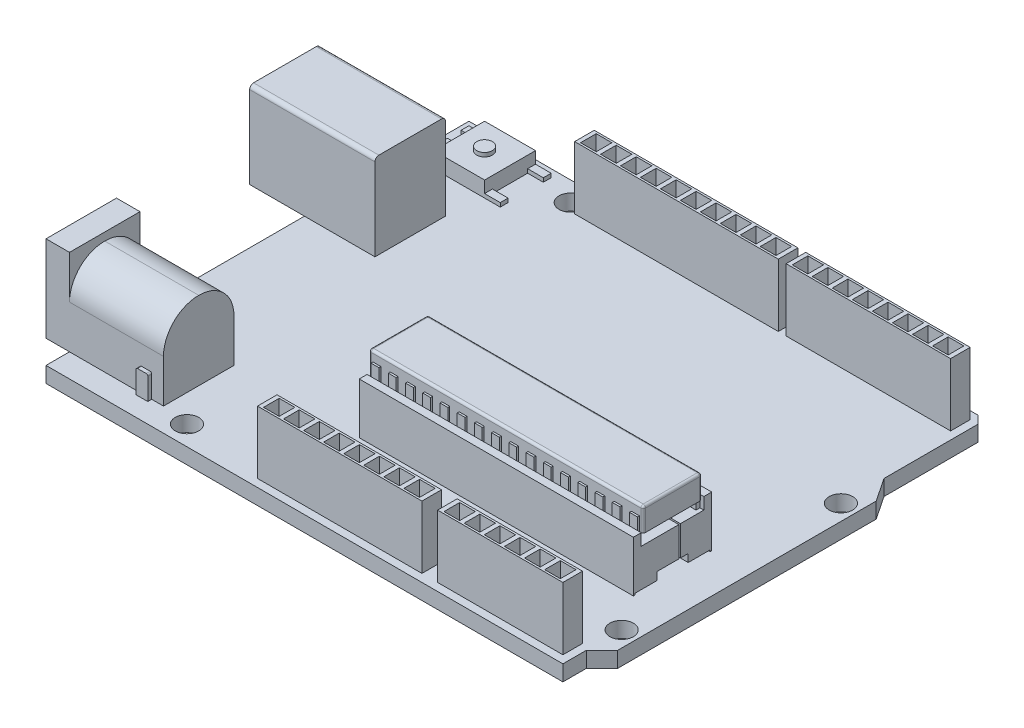
SolidWorks part; units mm, degrees
ref_plane "Ön Düzlem" through (0, 0, 0) normal (0, 0, 1) x (1, 0, 0)
ref_plane "Üst Düzlem" through (0, 0, 0) normal (0, 1, 0) x (1, 0, 0)
ref_plane "Sağ Düzlem" through (0, 0, 0) normal (1, 0, 0) x (0, 0, -1)
sketch "Çizim2" plane through (0, 0, 0) normal (0, 1, 0) x (1, 0, 0)
  line L0 (32, -27) -> (32, -19.8418) construction
  line L1 (-34, 27) -> (31, 27)
  line L2 (-34, 27) -> (-34, -27)
  line L3 (-34, -27) -> (32, -27)
  line L4 (34, 11) -> (34, -22)
  line L5 (-34, 27) -> (32, -25.4118) construction
  line L6 (-34, -27) -> (32, 25.4118) construction
  line L7 (32, -27) -> (32, -24)
  line L8 (32, -24) -> (34, -22)
  line L9 (32, 27) -> (32, 12.4131) construction
  line L10 (34, 11) -> (32, 14)
  line L11 (32, 14) -> (32, 26)
  line L12 (31, 27) -> (32, 26)
  line L13 (32, 14) -> (32, -24) construction
  line L14 (34, -22) -> (-34, -22) construction
  line L15 (-17, 27) -> (-17, 17.3329) construction
  line L16 (-34, 26) -> (4.5999, 26) construction
  line L17 (-18.5, 24.5) -> (-18.5, -27) construction
  circle A0 centre (32, -19.5) radius 1.5
  circle A1 centre (32, 8.5) radius 1.5
  circle A2 centre (-18.5, 24.5) radius 1.5
  circle A3 centre (-18.5, -24.5) radius 1.5
  point P0 (0, 0)
  point P1 (34, 11)
  point P6 (32, -27)
  point P7 (34, -22)
  point P10 (32, -24)
  point P14 (32, 27)
  point P15 (32, 14)
  point P27 (-17, 27)
  dimension "D1" = 3
  dimension "D7" = 3
  dimension "D9" = 28
  dimension "D10" = 2.5
  dimension "D13" = 3
  dimension "D14" = 3
  dimension "D2" = 33
  dimension "D3" = 66
  dimension "D4" = 66
  dimension "D5" = 3
  dimension "D6" = 13
  dimension "D11" = 49
  dimension "D12" = 1
  dimension "D15" = 2.5
extrude "Yükseklik-Ekstrüzyon1" add sketch "Çizim2" along normal blind 2
sketch "Çizim3" plane through (0, 2, 0) normal (0, 1, 0) x (1, 0, 0)
  line L0 (-34, 27) -> (-34, -27) construction
  line L1 (-31, 26) -> (-24.5, 26)
  line L2 (-31, 26) -> (-31, 19.5)
  line L3 (-31, 19.5) -> (-24.5, 19.5)
  line L4 (-24.5, 26) -> (-24.5, 19.5)
  line L5 (-31, 26) -> (-24.5, 19.5) construction
  line L6 (-31, 19.5) -> (-24.5, 26) construction
  line L7 (31, 27) -> (-34, 27) construction
  point P0 (-27.75, 22.75)
  dimension "D1" = 6.5
  dimension "D2" = 6.5
  dimension "D3" = 3
  dimension "D4" = 1
extrude "Yükseklik-Ekstrüzyon2" add sketch "Çizim3" along normal blind 2
sketch "Çizim4" plane through (0, 4, 0) normal (0, 1, 0) x (1, 0, 0)
  line L0 (-31, 26) -> (-24.5, 19.5) construction
  circle A0 centre (-27.75, 22.75) radius 1
  dimension "D1" = 2
extrude "Yükseklik-Ekstrüzyon3" add sketch "Çizim4" along normal blind 0.5
sketch "Çizim5" plane through (0, 2, 0) normal (0, 1, 0) x (1, 0, 0)
  line L1 (-34, 27) -> (-34, -27) construction
  line L2 (-31, 26) -> (-31, 19.5) construction
  line L3 (-31, 23.25) -> (-33, 23.25)
  line L4 (-31, 26) -> (-33, 26)
  line L5 (-31, 22.25) -> (-33, 22.25)
  line L6 (-33, 23.25) -> (-33, 22.25)
  line L7 (-31, 22.75) -> (-33, 22.25) construction
  line L8 (-31, 22.75) -> (-33, 23.25) construction
  line L9 (-31, 23.25) -> (-31, 22.25)
  line L10 (-31, 22.75) -> (-34, 22.75) construction
  line L11 (-31, 26) -> (-31, 25)
  line L12 (-31, 25) -> (-33, 25)
  line L13 (-33, 26) -> (-33, 25)
  line L14 (-31, 19.5) -> (-33, 19.5)
  line L15 (-31, 19.5) -> (-31, 20.5)
  line L16 (-31, 20.5) -> (-33, 20.5)
  line L17 (-33, 19.5) -> (-33, 20.5)
  line L18 (-24.5, 26) -> (-22.5, 26)
  line L19 (-24.5, 26) -> (-24.5, 25)
  line L20 (-24.5, 25) -> (-22.5, 25)
  line L21 (-22.5, 26) -> (-22.5, 25)
  line L22 (-24.5, 19.5) -> (-22.5, 19.5)
  line L23 (-24.5, 19.5) -> (-24.5, 20.5)
  line L24 (-24.5, 20.5) -> (-22.5, 20.5)
  line L25 (-22.5, 19.5) -> (-22.5, 20.5)
  point P5 (-31, 22.75)
  dimension "D1" = 1
  dimension "D2" = 1
  dimension "D3" = 1
  dimension "D4" = 1
  dimension "D5" = 2
extrude "Yükseklik-Ekstrüzyon4" add sketch "Çizim5" along normal blind 0.5
sketch "Çizim6" plane through (0, 2, 0) normal (0, 1, 0) x (1, 0, 0)
  line L0 (-34, 6) -> (34, 6) construction
  line L1 (-34, 27) -> (-34, -27) construction
  line L2 (34, -22) -> (34, 11) construction
  line L3 (31, 27) -> (-34, 27) construction
  line L5 (-25, 6) -> (-41, 6)
  line L6 (-25, 6) -> (-25, 15)
  line L7 (-25, 15) -> (-41, 15)
  line L8 (-41, 6) -> (-41, 15)
  point P8 (-25, 6)
  dimension "D1" = 21
  dimension "D2" = 9
  dimension "D3" = 16
  dimension "D4" = 9
extrude "Yükseklik-Ekstrüzyon5" add sketch "Çizim6" along normal blind 11
sketch "Çizim7" plane through (-41, 0, 0) normal (-1, 0, 0) x (0, 0, 1)
  line L0 (-14, 3.5) -> (-7, 3.5)
  line L1 (-15, 13) -> (-15, 2) construction
  line L2 (-6, 13) -> (-6, 2) construction
  line L3 (-15, 2) -> (-6, 2) construction
  line L4 (-14, 3.5) -> (-14, 10.5)
  line L5 (-15, 13) -> (-6, 13) construction
  line L6 (-12.5, 12) -> (-8.5, 12)
  line L7 (-7, 10.5) -> (-7, 3.5)
  line L9 (-8.5, 12) -> (-7, 10.5)
  line L10 (-14, 10.5) -> (-12.5, 12)
  point P12 (-14, 12)
  point P19 (-7, 12)
  point P20 (-14, 12)
  dimension "D1" = 1.5
  dimension "D2" = 1
  dimension "D3" = 1
  dimension "D5" = 1
extrude "Kes-Ekstrüzyon1" cut sketch "Çizim7" against normal blind 11
sketch "Çizim8" plane through (-30, 0, 0) normal (-1, 0, 0) x (0, 0, 1)
  line L0 (-14, 7) -> (-7, 7) construction
  line L1 (-14, 10.5) -> (-14, 3.5) construction
  line L2 (-7, 3.5) -> (-7, 10.5) construction
  line L4 (-13.25, 8.5) -> (-7.75, 8.5)
  line L5 (-13.25, 8.5) -> (-13.25, 5.5)
  line L6 (-13.25, 5.5) -> (-7.75, 5.5)
  line L7 (-7.75, 8.5) -> (-7.75, 5.5)
  line L8 (-13.25, 8.5) -> (-7.75, 5.5) construction
  line L9 (-13.25, 5.5) -> (-7.75, 8.5) construction
  point P6 (-10.5, 7)
  dimension "D1" = 5.5
  dimension "D2" = 3
extrude "Yükseklik-Ekstrüzyon6" add sketch "Çizim8" along normal blind 11
fillet "Radyus1" radius 0.5 1 edges at (-33, 13, -6)
fillet "Radyus2" radius 0.5 1 edges at (-33, 13, -15)
sketch "Çizim9" plane through (0, 2, 0) normal (0, 1, 0) x (1, 0, 0)
  line L0 (-34, -24) -> (8.4522, -24) construction
  line L3 (-34, 6) -> (-34, -27) construction
  line L4 (-34, -27) -> (32, -27) construction
  line L6 (-34, -24) -> (-22, -24)
  line L7 (-34, -24) -> (-34, -15)
  line L8 (-34, -15) -> (-22, -15)
  line L9 (-22, -24) -> (-22, -15)
  dimension "D1" = 3
  dimension "D2" = 12
  dimension "D3" = 9
extrude "Yükseklik-Ekstrüzyon7" add sketch "Çizim9" along normal blind 10
fillet "Radyus3" radius 4.5 1 edges at (-28, 12, 15)
fillet "Radyus4" radius 4.5 3 edges at (-28, 12, 24) (-22, 12, 21.75) (-34, 12, 21.75)
sketch "Çizim10" plane through (-34, 0, 0) normal (-1, 0, 0) x (0, 0, 1)
  line L1 (15, 2) -> (24, 2)
  line L2 (15, 2) -> (15, 13)
  line L3 (15, 13) -> (24, 13)
  line L4 (24, 2) -> (24, 13)
  dimension "D1" = 11
  dimension "D2" = 9
extrude "Yükseklik-Ekstrüzyon8" add sketch "Çizim10" along normal blind 3
sketch "Çizim11" plane through (-37, 0, 0) normal (-1, 0, 0) x (0, 0, 1)
  line L0 (15, 8) -> (24, 8) construction
  line L1 (15, 13) -> (15, 2) construction
  line L2 (24, 2) -> (24, 13) construction
  line L3 (24, 13) -> (15, 13) construction
  circle A0 centre (19.5, 8) radius 3
  dimension "D2" = 6
  dimension "D1" = 5
extrude "Kes-Ekstrüzyon2" cut sketch "Çizim11" against normal blind 8
sketch "Çizim12" plane through (-29, 0, 0) normal (-1, 0, 0) x (0, 0, 1)
  circle A0 centre (19.5, 8) radius 0.5
  dimension "D1" = 1
extrude "Yükseklik-Ekstrüzyon9" add sketch "Çizim12" along normal blind 7 contours A0
sketch "Çizim13" plane through (0, 0, 24) normal (0, 0, 1) x (1, 0, 0)
  line L0 (-34, 2) -> (-22, 2) construction
  line L1 (-25, 2) -> (-23.5, 2)
  line L2 (-25, 2) -> (-25, 5)
  line L3 (-25, 5) -> (-23.5, 5)
  line L4 (-23.5, 2) -> (-23.5, 5)
  line L5 (-22, 7.5) -> (-22, 2) construction
  dimension "D1" = 3
  dimension "D2" = 1.5
  dimension "D3" = 1.5
extrude "Yükseklik-Ekstrüzyon10" add sketch "Çizim13" along normal blind 0.5
fillet "Radyus5" radius 0.2 1 edges at (-23.5, 5, 24.25)
fillet "Radyus6" radius 0.2 1 edges at (-25, 5, 24.25)
sketch "Çizim15" plane through (0, 0, 15) normal (0, 0, -1) x (-1, 0, 0)
  line L0 (22, 2) -> (34, 2) construction
  line L1 (23.5, 2) -> (25, 2)
  line L2 (23.5, 2) -> (23.5, 5)
  line L3 (23.5, 5) -> (25, 5)
  line L4 (25, 2) -> (25, 5)
  line L5 (22, 7.5) -> (22, 2) construction
  dimension "D1" = 1.5
  dimension "D2" = 1.5
  dimension "D3" = 3
extrude "Yükseklik-Ekstrüzyon11" add sketch "Çizim15" along normal blind 0.5
fillet "Radyus7" radius 0.2 1 edges at (-23.5, 5, 14.75)
fillet "Radyus8" radius 0.2 1 edges at (-25, 5, 14.75)
fillet "Radyus9" radius 0.3 1 edges at (-36, 8, 20)
sketch "Çizim16" plane through (0, 2, 0) normal (0, 1, 0) x (1, 0, 0)
  line L0 (34, -15) -> (9.0566, -15) construction
  line L1 (34, -22) -> (34, 11) construction
  line L2 (-34, -27) -> (32, -27) construction
  line L4 (29, -15) -> (-6, -15)
  line L5 (29, -15) -> (29, -5)
  line L6 (29, -5) -> (-6, -5)
  line L7 (-6, -15) -> (-6, -5)
  dimension "D1" = 12
  dimension "D2" = 5
  dimension "D3" = 10
  dimension "D4" = 35
extrude "Yükseklik-Ekstrüzyon12" add sketch "Çizim16" along normal blind 5
sketch "Çizim17" plane through (0, 7, 0) normal (0, 1, 0) x (1, 0, 0)
  line L0 (29, -15) -> (29, -5) construction
  line L1 (-6, -5) -> (29, -5)
  line L2 (-6, -5) -> (-6, -6)
  line L3 (-6, -6) -> (29, -6)
  line L4 (29, -5) -> (29, -6)
  line L5 (-6, -5) -> (-6, -15) construction
  line L6 (29, -15) -> (-6, -15)
  line L7 (29, -15) -> (29, -14)
  line L8 (29, -14) -> (-6, -14)
  line L9 (-6, -15) -> (-6, -14)
  dimension "D1" = 1
  dimension "D2" = 1
extrude "Yükseklik-Ekstrüzyon13" add sketch "Çizim17" along normal blind 1.5
sketch "Çizim18" plane through (0, 7, 0) normal (0, 1, 0) x (1, 0, 0)
  line L0 (-6, -10) -> (9.4618, -10) construction
  line L1 (-6, -5) -> (-6, -15) construction
  line L2 (-6, -6) -> (29, -6) construction
  line L3 (-5.5, -6) -> (-4.5, -6)
  line L4 (-5.5, -6) -> (-5.5, -6.5)
  line L5 (-5.5, -6.5) -> (-4.5, -6.5)
  line L6 (-4.5, -6) -> (-4.5, -6.5)
  line L7 (-6, -6) -> (-6, -14) construction
  line L8 (-3.3, -6) -> (-3.3, -6.5)
  line L9 (-3.3, -6.5) -> (-2.3, -6.5)
  line L10 (-3.3, -6) -> (-2.3, -6)
  line L11 (-2.3, -6) -> (-2.3, -6.5)
  line L12 (-1.1, -6) -> (-1.1, -6.5)
  line L13 (-1.1, -6.5) -> (-0.1, -6.5)
  line L14 (-1.1, -6) -> (-0.1, -6)
  line L15 (-0.1, -6) -> (-0.1, -6.5)
  line L16 (1.1, -6) -> (1.1, -6.5)
  line L17 (1.1, -6.5) -> (2.1, -6.5)
  line L18 (1.1, -6) -> (2.1, -6)
  line L19 (2.1, -6) -> (2.1, -6.5)
  line L20 (3.3, -6) -> (3.3, -6.5)
  line L21 (3.3, -6.5) -> (4.3, -6.5)
  line L22 (3.3, -6) -> (4.3, -6)
  line L23 (4.3, -6) -> (4.3, -6.5)
  line L24 (5.5, -6) -> (5.5, -6.5)
  line L25 (5.5, -6.5) -> (6.5, -6.5)
  line L26 (5.5, -6) -> (6.5, -6)
  line L27 (6.5, -6) -> (6.5, -6.5)
  line L28 (7.7, -6) -> (7.7, -6.5)
  line L29 (7.7, -6.5) -> (8.7, -6.5)
  line L30 (7.7, -6) -> (8.7, -6)
  line L31 (8.7, -6) -> (8.7, -6.5)
  line L32 (9.9, -6) -> (9.9, -6.5)
  line L33 (9.9, -6.5) -> (10.9, -6.5)
  line L34 (9.9, -6) -> (10.9, -6)
  line L35 (10.9, -6) -> (10.9, -6.5)
  line L36 (12.1, -6) -> (12.1, -6.5)
  line L37 (12.1, -6.5) -> (13.1, -6.5)
  line L38 (12.1, -6) -> (13.1, -6)
  line L39 (13.1, -6) -> (13.1, -6.5)
  line L40 (14.3, -6) -> (14.3, -6.5)
  line L41 (14.3, -6.5) -> (15.3, -6.5)
  line L42 (14.3, -6) -> (15.3, -6)
  line L43 (15.3, -6) -> (15.3, -6.5)
  line L44 (16.5, -6) -> (16.5, -6.5)
  line L45 (16.5, -6.5) -> (17.5, -6.5)
  line L46 (16.5, -6) -> (17.5, -6)
  line L47 (17.5, -6) -> (17.5, -6.5)
  line L48 (18.7, -6) -> (18.7, -6.5)
  line L49 (18.7, -6.5) -> (19.7, -6.5)
  line L50 (18.7, -6) -> (19.7, -6)
  line L51 (19.7, -6) -> (19.7, -6.5)
  line L52 (20.9, -6) -> (20.9, -6.5)
  line L53 (20.9, -6.5) -> (21.9, -6.5)
  line L54 (20.9, -6) -> (21.9, -6)
  line L55 (21.9, -6) -> (21.9, -6.5)
  line L56 (23.1, -6) -> (23.1, -6.5)
  line L57 (23.1, -6.5) -> (24.1, -6.5)
  line L58 (23.1, -6) -> (24.1, -6)
  line L59 (24.1, -6) -> (24.1, -6.5)
  line L60 (25.3, -6) -> (25.3, -6.5)
  line L61 (25.3, -6.5) -> (26.3, -6.5)
  line L62 (25.3, -6) -> (26.3, -6)
  line L63 (26.3, -6) -> (26.3, -6.5)
  line L64 (27.5, -6) -> (27.5, -6.5)
  line L65 (27.5, -6.5) -> (28.5, -6.5)
  line L66 (27.5, -6) -> (28.5, -6)
  line L67 (28.5, -6) -> (28.5, -6.5)
  line L68 (28.5, -14) -> (28.5, -13.5)
  line L69 (27.5, -14) -> (28.5, -14)
  line L70 (27.5, -13.5) -> (28.5, -13.5)
  line L71 (27.5, -14) -> (27.5, -13.5)
  line L72 (26.3, -14) -> (26.3, -13.5)
  line L73 (25.3, -14) -> (26.3, -14)
  line L74 (25.3, -13.5) -> (26.3, -13.5)
  line L75 (25.3, -14) -> (25.3, -13.5)
  line L76 (24.1, -14) -> (24.1, -13.5)
  line L77 (23.1, -14) -> (24.1, -14)
  line L78 (23.1, -13.5) -> (24.1, -13.5)
  line L79 (23.1, -14) -> (23.1, -13.5)
  line L80 (21.9, -14) -> (21.9, -13.5)
  line L81 (20.9, -14) -> (21.9, -14)
  line L82 (20.9, -13.5) -> (21.9, -13.5)
  line L83 (20.9, -14) -> (20.9, -13.5)
  line L84 (19.7, -14) -> (19.7, -13.5)
  line L85 (18.7, -14) -> (19.7, -14)
  line L86 (18.7, -13.5) -> (19.7, -13.5)
  line L87 (18.7, -14) -> (18.7, -13.5)
  line L88 (17.5, -14) -> (17.5, -13.5)
  line L89 (16.5, -14) -> (17.5, -14)
  line L90 (16.5, -13.5) -> (17.5, -13.5)
  line L91 (16.5, -14) -> (16.5, -13.5)
  line L92 (15.3, -14) -> (15.3, -13.5)
  line L93 (14.3, -14) -> (15.3, -14)
  line L94 (14.3, -13.5) -> (15.3, -13.5)
  line L95 (14.3, -14) -> (14.3, -13.5)
  line L96 (13.1, -14) -> (13.1, -13.5)
  line L97 (12.1, -14) -> (13.1, -14)
  line L98 (12.1, -13.5) -> (13.1, -13.5)
  line L99 (12.1, -14) -> (12.1, -13.5)
  line L100 (10.9, -14) -> (10.9, -13.5)
  line L101 (9.9, -14) -> (10.9, -14)
  line L102 (9.9, -13.5) -> (10.9, -13.5)
  line L103 (9.9, -14) -> (9.9, -13.5)
  line L104 (8.7, -14) -> (8.7, -13.5)
  line L105 (7.7, -14) -> (8.7, -14)
  line L106 (7.7, -13.5) -> (8.7, -13.5)
  line L107 (7.7, -14) -> (7.7, -13.5)
  line L108 (6.5, -14) -> (6.5, -13.5)
  line L109 (5.5, -14) -> (6.5, -14)
  line L110 (5.5, -13.5) -> (6.5, -13.5)
  line L111 (5.5, -14) -> (5.5, -13.5)
  line L112 (4.3, -14) -> (4.3, -13.5)
  line L113 (3.3, -14) -> (4.3, -14)
  line L114 (3.3, -13.5) -> (4.3, -13.5)
  line L115 (3.3, -14) -> (3.3, -13.5)
  line L116 (2.1, -14) -> (2.1, -13.5)
  line L117 (1.1, -14) -> (2.1, -14)
  line L118 (1.1, -13.5) -> (2.1, -13.5)
  line L119 (1.1, -14) -> (1.1, -13.5)
  line L120 (-0.1, -14) -> (-0.1, -13.5)
  line L121 (-1.1, -14) -> (-0.1, -14)
  line L122 (-1.1, -13.5) -> (-0.1, -13.5)
  line L123 (-1.1, -14) -> (-1.1, -13.5)
  line L124 (-2.3, -14) -> (-2.3, -13.5)
  line L125 (-3.3, -14) -> (-2.3, -14)
  line L126 (-3.3, -13.5) -> (-2.3, -13.5)
  line L127 (-3.3, -14) -> (-3.3, -13.5)
  line L128 (-4.5, -14) -> (-4.5, -13.5)
  line L129 (-5.5, -14) -> (-4.5, -14)
  line L130 (-5.5, -13.5) -> (-4.5, -13.5)
  line L131 (-5.5, -14) -> (-5.5, -13.5)
  dimension "D1" = 0.5
  dimension "D2" = 1
  dimension "D3" = 0.5
  dimension "D4" = 16
extrude "Yükseklik-Ekstrüzyon14" add sketch "Çizim18" along normal blind 3
ref_plane "Düzlem1" through (0, 8.75, 0) normal (0, 1, 0) x (1, 0, 0)
sketch "Çizim19" plane through (0, 8.75, 0) normal (0, 1, 0) x (1, 0, 0)
  line L0 (-5.5, -6.25) -> (-6, -6.25) construction
  line L1 (-5.5, -6) -> (-5.5, -6.5) construction
  line L2 (-6, -6) -> (-6, -14) construction
  line L3 (29, -15) -> (29, -5) construction
  line L4 (-6, -6.25) -> (29, -6.25)
  line L5 (-6, -6.25) -> (-6, -13.75)
  line L6 (-6, -13.75) -> (29, -13.75)
  line L7 (29, -6.25) -> (29, -13.75)
extrude "Yükseklik-Ekstrüzyon15" add sketch "Çizim19" along normal blind 2.5 and the other way blind 0.5
fillet "Radyus10" radius 0.3 1 edges at (11.5, 11.25, 13.75)
fillet "Radyus11" radius 0.3 1 edges at (11.5, 11.25, 6.25)
fillet "Radyus12" radius 0.3 5 edges at (29, 9.6, 13.75) (29, 9.6, 6.25) (29, 11.25, 10) (29, 11.1621, 13.6621) (29, 11.1621, 6.3379)
fillet "Radyus13" radius 0.3 5 edges at (-6, 9.6, 13.75) (-6, 11.1621, 13.6621) (-6, 11.25, 10) (-6, 11.1621, 6.3379) (-6, 9.6, 6.25)
sketch "Çizim20" plane through (29, 0, 0) normal (1, 0, 0) x (0, 0, -1)
  line L0 (-22, 2) -> (11, 2) construction
  line L1 (-14.8, 2) -> (-5.2, 2)
  line L2 (-14.8, 2) -> (-14.8, 2.2)
  line L3 (-14.8, 2.2) -> (-12, 2.2)
  line L4 (-5.2, 2) -> (-5.2, 2.2)
  line L5 (-5, 8.5) -> (-5, 2) construction
  line L6 (-15, 8.5) -> (-15, 2) construction
  line L7 (-8, 2.2) -> (-5.2, 2.2)
  line L8 (-9, 3.2) -> (-9, 7)
  line L9 (-12, 2.2) -> (-12, 3.2)
  line L10 (-12, 3.2) -> (-9.2, 3.2)
  line L11 (-8, 2.2) -> (-8, 3.2)
  line L12 (-14, 7) -> (-6, 7) construction
  line L13 (-9, 7) -> (-9.2, 7)
  line L14 (-9.2, 7) -> (-9.2, 3.2)
  line L15 (-9, 3.2) -> (-8, 3.2)
  point P10 (-10, 2.2)
  dimension "D1" = 0.2
  dimension "D2" = 0.2
  dimension "D3" = 0.2
  dimension "D4" = 4
  dimension "D5" = 0.2
  dimension "D6" = 1
extrude "Kes-Ekstrüzyon3" cut sketch "Çizim20" against normal up to next
sketch "Çizim21" plane through (0, 2, 0) normal (0, 1, 0) x (1, 0, 0)
  line L0 (31, -27) -> (31, -25.867) construction
  line L1 (-34, -27) -> (32, -27) construction
  line L2 (32, -27) -> (32, -24) construction
  line L3 (32, -26) -> (30.217, -26) construction
  line L4 (15, -24.75) -> (31, -24.75) construction
  line L5 (31, -26) -> (15, -26)
  line L6 (31, -26) -> (31, -23.5)
  line L7 (31, -23.5) -> (15, -23.5)
  line L8 (15, -26) -> (15, -23.5)
  line L9 (18.1414, -23.75) -> (20.1414, -23.75)
  line L10 (15.5714, -23.75) -> (17.5714, -23.75)
  line L11 (15.5714, -23.75) -> (15.5714, -25.75)
  line L12 (15.5714, -25.75) -> (17.5714, -25.75)
  line L13 (17.5714, -23.75) -> (17.5714, -25.75)
  line L14 (15.5714, -23.75) -> (17.5714, -25.75) construction
  line L15 (15.5714, -25.75) -> (17.5714, -23.75) construction
  line L16 (18.1414, -23.75) -> (18.1414, -25.75)
  line L17 (18.1414, -25.75) -> (20.1414, -25.75)
  line L18 (20.1414, -23.75) -> (20.1414, -25.75)
  line L19 (20.7114, -23.75) -> (22.7114, -23.75)
  line L20 (20.7114, -23.75) -> (20.7114, -25.75)
  line L21 (20.7114, -25.75) -> (22.7114, -25.75)
  line L22 (22.7114, -23.75) -> (22.7114, -25.75)
  line L23 (23.2814, -23.75) -> (25.2814, -23.75)
  line L24 (23.2814, -23.75) -> (23.2814, -25.75)
  line L25 (23.2814, -25.75) -> (25.2814, -25.75)
  line L26 (25.2814, -23.75) -> (25.2814, -25.75)
  line L27 (25.8514, -23.75) -> (27.8514, -23.75)
  line L28 (25.8514, -23.75) -> (25.8514, -25.75)
  line L29 (25.8514, -25.75) -> (27.8514, -25.75)
  line L30 (27.8514, -23.75) -> (27.8514, -25.75)
  line L31 (28.4214, -23.75) -> (30.4214, -23.75)
  line L32 (28.4214, -23.75) -> (28.4214, -25.75)
  line L33 (28.4214, -25.75) -> (30.4214, -25.75)
  line L34 (30.4214, -23.75) -> (30.4214, -25.75)
  line L35 (15, -24.75) -> (13, -24.75) construction
  line L36 (-8, -24.75) -> (-10.4407, -24.75) construction
  line L37 (13, -26) -> (-8, -26)
  line L38 (13, -26) -> (13, -23.5)
  line L39 (13, -23.5) -> (-8, -23.5)
  line L40 (-8, -26) -> (-8, -23.5)
  line L41 (13, -24.75) -> (-8, -24.75) construction
  line L42 (7.8844, -23.75) -> (7.8844, -25.75)
  line L43 (10.4444, -23.75) -> (12.4444, -23.75)
  line L44 (10.4444, -23.75) -> (10.4444, -25.75)
  line L45 (10.4444, -25.75) -> (12.4444, -25.75)
  line L46 (12.4444, -23.75) -> (12.4444, -25.75)
  line L47 (10.4444, -23.75) -> (12.4444, -25.75) construction
  line L48 (10.4444, -25.75) -> (12.4444, -23.75) construction
  line L49 (7.8844, -23.75) -> (9.8844, -23.75)
  line L50 (9.8844, -23.75) -> (9.8844, -25.75)
  line L51 (7.8844, -25.75) -> (9.8844, -25.75)
  line L52 (5.3244, -23.75) -> (5.3244, -25.75)
  line L53 (5.3244, -23.75) -> (7.3244, -23.75)
  line L54 (7.3244, -23.75) -> (7.3244, -25.75)
  line L55 (5.3244, -25.75) -> (7.3244, -25.75)
  line L56 (2.7644, -23.75) -> (2.7644, -25.75)
  line L57 (2.7644, -23.75) -> (4.7644, -23.75)
  line L58 (4.7644, -23.75) -> (4.7644, -25.75)
  line L59 (2.7644, -25.75) -> (4.7644, -25.75)
  line L60 (0.2044, -23.75) -> (0.2044, -25.75)
  line L61 (0.2044, -23.75) -> (2.2044, -23.75)
  line L62 (2.2044, -23.75) -> (2.2044, -25.75)
  line L63 (0.2044, -25.75) -> (2.2044, -25.75)
  line L64 (-2.3556, -23.75) -> (-2.3556, -25.75)
  line L65 (-2.3556, -23.75) -> (-0.3556, -23.75)
  line L66 (-0.3556, -23.75) -> (-0.3556, -25.75)
  line L67 (-2.3556, -25.75) -> (-0.3556, -25.75)
  line L68 (-4.9156, -23.75) -> (-4.9156, -25.75)
  line L69 (-4.9156, -23.75) -> (-2.9156, -23.75)
  line L70 (-2.9156, -23.75) -> (-2.9156, -25.75)
  line L71 (-4.9156, -25.75) -> (-2.9156, -25.75)
  line L72 (-7.4756, -23.75) -> (-7.4756, -25.75)
  line L73 (-7.4756, -23.75) -> (-5.4756, -23.75)
  line L74 (-5.4756, -23.75) -> (-5.4756, -25.75)
  line L75 (-7.4756, -25.75) -> (-5.4756, -25.75)
  point P14 (16.5714, -24.75)
  point P15 (16.5714, -24.75)
  point P20 (13, -24.75)
  point P48 (11.4444, -24.75)
  dimension "D1" = 1
  dimension "D2" = 1
  dimension "D3" = 2.5
  dimension "D4" = 16
  dimension "D5" = 2
  dimension "D6" = 2
  dimension "D7" = 0.5714
  dimension "D9" = 2
  dimension "D10" = 1.25
  dimension "D11" = 21
  dimension "D12" = 2
  dimension "D13" = 2
  dimension "D14" = 0.5556
  dimension "D8" = 6
  dimension "D15" = 8
extrude "Yükseklik-Ekstrüzyon16" add sketch "Çizim21" along normal blind 8
sketch "Çizim22" plane through (0, 2, 0) normal (0, 1, 0) x (1, 0, 0)
  line L0 (31, 22.3242) -> (31, 31.1831) construction
  line L2 (32, 14) -> (32, 26) construction
  line L4 (31, 26) -> (20.6446, 26) construction
  line L5 (31, 27) -> (-34, 27) construction
  line L6 (31, 24.75) -> (9, 24.75) construction
  line L7 (31, 26) -> (10, 26)
  line L8 (31, 26) -> (31, 23.5)
  line L9 (31, 23.5) -> (10, 23.5)
  line L10 (10, 26) -> (10, 23.5)
  line L11 (25.8844, 25.75) -> (25.8844, 23.75)
  line L12 (28.4444, 25.75) -> (30.4444, 25.75)
  line L13 (28.4444, 25.75) -> (28.4444, 23.75)
  line L14 (28.4444, 23.75) -> (30.4444, 23.75)
  line L15 (30.4444, 25.75) -> (30.4444, 23.75)
  line L16 (28.4444, 25.75) -> (30.4444, 23.75) construction
  line L17 (28.4444, 23.75) -> (30.4444, 25.75) construction
  line L18 (25.8844, 25.75) -> (27.8844, 25.75)
  line L19 (27.8844, 25.75) -> (27.8844, 23.75)
  line L20 (25.8844, 23.75) -> (27.8844, 23.75)
  line L21 (23.3244, 25.75) -> (23.3244, 23.75)
  line L22 (23.3244, 25.75) -> (25.3244, 25.75)
  line L23 (25.3244, 25.75) -> (25.3244, 23.75)
  line L24 (23.3244, 23.75) -> (25.3244, 23.75)
  line L25 (20.7644, 25.75) -> (20.7644, 23.75)
  line L26 (20.7644, 25.75) -> (22.7644, 25.75)
  line L27 (22.7644, 25.75) -> (22.7644, 23.75)
  line L28 (20.7644, 23.75) -> (22.7644, 23.75)
  line L29 (18.2044, 25.75) -> (18.2044, 23.75)
  line L30 (18.2044, 25.75) -> (20.2044, 25.75)
  line L31 (20.2044, 25.75) -> (20.2044, 23.75)
  line L32 (18.2044, 23.75) -> (20.2044, 23.75)
  line L33 (15.6444, 25.75) -> (15.6444, 23.75)
  line L34 (15.6444, 25.75) -> (17.6444, 25.75)
  line L35 (17.6444, 25.75) -> (17.6444, 23.75)
  line L36 (15.6444, 23.75) -> (17.6444, 23.75)
  line L37 (13.0844, 25.75) -> (13.0844, 23.75)
  line L38 (13.0844, 25.75) -> (15.0844, 25.75)
  line L39 (15.0844, 25.75) -> (15.0844, 23.75)
  line L40 (13.0844, 23.75) -> (15.0844, 23.75)
  line L41 (10.5244, 25.75) -> (10.5244, 23.75)
  line L42 (10.5244, 25.75) -> (12.5244, 25.75)
  line L43 (12.5244, 25.75) -> (12.5244, 23.75)
  line L44 (10.5244, 23.75) -> (12.5244, 23.75)
  line L45 (9, 23.5) -> (-17, 23.5)
  line L46 (9, 24.75) -> (4.0508, 24.75) construction
  line L47 (9, 23.5) -> (9, 26)
  line L48 (9, 26) -> (-17, 26)
  line L49 (-17, 23.5) -> (-17, 26)
  line L50 (3.9045, 25.75) -> (5.9045, 25.75)
  line L51 (6.4545, 25.75) -> (8.4545, 25.75)
  line L52 (6.4545, 25.75) -> (6.4545, 23.75)
  line L53 (6.4545, 23.75) -> (8.4545, 23.75)
  line L54 (8.4545, 25.75) -> (8.4545, 23.75)
  line L55 (6.4545, 25.75) -> (8.4545, 23.75) construction
  line L56 (6.4545, 23.75) -> (8.4545, 25.75) construction
  line L57 (3.9045, 25.75) -> (3.9045, 23.75)
  line L58 (3.9045, 23.75) -> (5.9045, 23.75)
  line L59 (5.9045, 25.75) -> (5.9045, 23.75)
  line L60 (1.3545, 25.75) -> (3.3545, 25.75)
  line L61 (1.3545, 25.75) -> (1.3545, 23.75)
  line L62 (1.3545, 23.75) -> (3.3545, 23.75)
  line L63 (3.3545, 25.75) -> (3.3545, 23.75)
  line L64 (-1.1955, 25.75) -> (0.8045, 25.75)
  line L65 (-1.1955, 25.75) -> (-1.1955, 23.75)
  line L66 (-1.1955, 23.75) -> (0.8045, 23.75)
  line L67 (0.8045, 25.75) -> (0.8045, 23.75)
  line L68 (-3.7455, 25.75) -> (-1.7455, 25.75)
  line L69 (-3.7455, 25.75) -> (-3.7455, 23.75)
  line L70 (-3.7455, 23.75) -> (-1.7455, 23.75)
  line L71 (-1.7455, 25.75) -> (-1.7455, 23.75)
  line L72 (-6.2955, 25.75) -> (-4.2955, 25.75)
  line L73 (-6.2955, 25.75) -> (-6.2955, 23.75)
  line L74 (-6.2955, 23.75) -> (-4.2955, 23.75)
  line L75 (-4.2955, 25.75) -> (-4.2955, 23.75)
  line L76 (-8.8455, 25.75) -> (-6.8455, 25.75)
  line L77 (-8.8455, 25.75) -> (-8.8455, 23.75)
  line L78 (-8.8455, 23.75) -> (-6.8455, 23.75)
  line L79 (-6.8455, 25.75) -> (-6.8455, 23.75)
  line L80 (-11.3955, 25.75) -> (-9.3955, 25.75)
  line L81 (-11.3955, 25.75) -> (-11.3955, 23.75)
  line L82 (-11.3955, 23.75) -> (-9.3955, 23.75)
  line L83 (-9.3955, 25.75) -> (-9.3955, 23.75)
  line L84 (-13.9455, 25.75) -> (-11.9455, 25.75)
  line L85 (-13.9455, 25.75) -> (-13.9455, 23.75)
  line L86 (-13.9455, 23.75) -> (-11.9455, 23.75)
  line L87 (-11.9455, 25.75) -> (-11.9455, 23.75)
  line L88 (-16.4955, 25.75) -> (-14.4955, 25.75)
  line L89 (-16.4955, 25.75) -> (-16.4955, 23.75)
  line L90 (-16.4955, 23.75) -> (-14.4955, 23.75)
  line L91 (-14.4955, 25.75) -> (-14.4955, 23.75)
  point P13 (29.4444, 24.75)
  point P18 (9, 24.75)
  point P50 (7.4545, 24.75)
  point P52 (-17, 24.75)
  dimension "D1" = 1
  dimension "D2" = 1
  dimension "D3" = 2.5
  dimension "D4" = 21
  dimension "D5" = 2
  dimension "D6" = 2
  dimension "D7" = 0.5556
  dimension "D9" = 1
  dimension "D10" = 26
  dimension "D11" = 1.25
  dimension "D12" = 2
  dimension "D13" = 2
  dimension "D14" = 0.5455
  dimension "D8" = 8
  dimension "D15" = 10
extrude "Yükseklik-Ekstrüzyon17" add sketch "Çizim22" along normal blind 8
sketch "Çizim29" [suppressed] plane through (0, 2, 0) normal (0, 1, 0) x (1, 0, 0)
  line L0 (-19.9959, -18) -> (12.3552, -18) construction
  line L1 (-34, -27) -> (32, -27) construction
  line L2 (-34, 6) -> (-34, -15) construction
  circle A0 centre (-16, -18) radius 3
  circle A1 centre (-9, -18) radius 3
  point P4 (-16, -18)
  dimension "D3" = 6
  dimension "D4" = 6
  dimension "D1" = 9
  dimension "D2" = 18
  dimension "D5" = 7
sketch "Çizim33" [suppressed] plane through (0, 2, 0) normal (0, 1, 0) x (1, 0, 0)
  line L0 (-34, 1) -> (-4.6187, 1) construction
  line L1 (-34, 6) -> (-34, -15) construction
  line L2 (-34, -27) -> (32, -27) construction
  line L3 (-9, 3.1205) -> (-9, -12.3055) construction
  line L4 (-9, -1.5) -> (-27.1631, -1.5) construction
  line L5 (-14.5, 1) -> (-14.5, -6.5826) construction
  line L6 (-17.5, -1.5) -> (-11.5, -1.5) construction
  line L7 (-17.5, 1) -> (-11.5, 1)
  line L8 (-17.5, -4) -> (-11.5, -4)
  arc A0 (-17.5, 1) -> (-17.5, -4) centre (-17.5, -1.5) ccw
  arc A1 (-11.5, -4) -> (-11.5, 1) centre (-11.5, -1.5) ccw
  point P14 (-14.5, -1.5)
  dimension "D6" = 8.5
  dimension "D1" = 28
  dimension "D2" = 25
  dimension "D3" = 2.5
  dimension "D4" = 5.5
  dimension "D5" = 5
